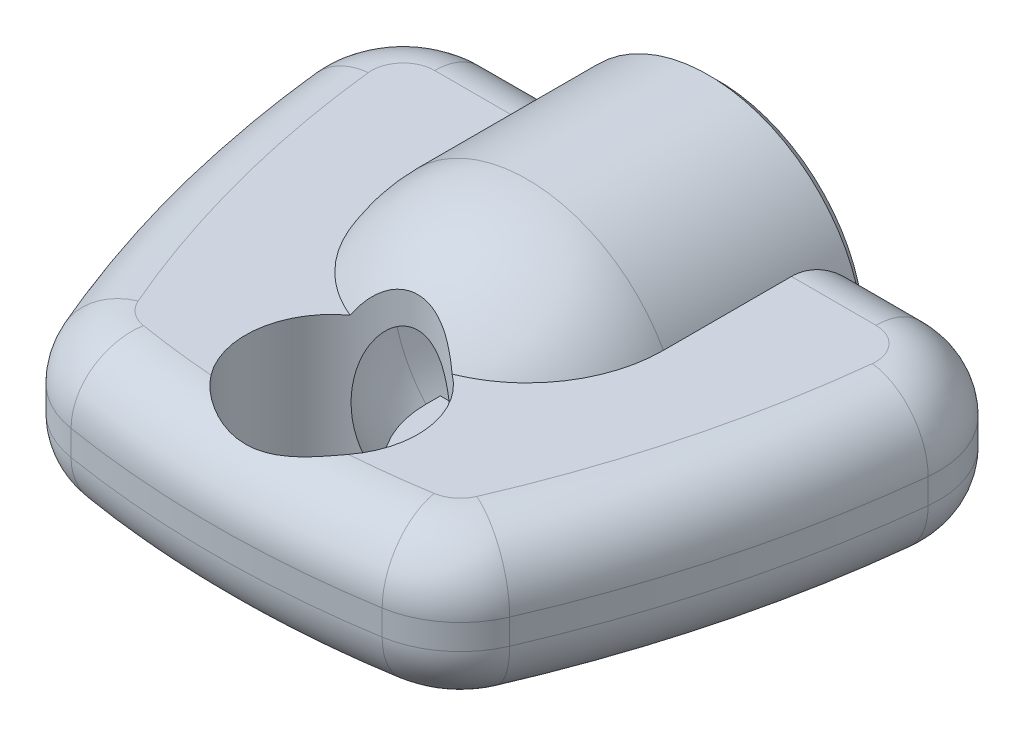
SolidWorks part; units mm, degrees
ref_plane "Front Plane" through (0, 0, 0) normal (0, 0, 1) x (1, 0, 0)
ref_plane "Top Plane" through (0, 0, 0) normal (0, 1, 0) x (1, 0, 0)
ref_plane "Right Plane" through (0, 0, 0) normal (1, 0, 0) x (0, 0, -1)
sketch "Sketch1" plane through (0, 0, 0) normal (0, 1, 0) x (1, 0, 0)
  line L0 (0, 0) -> (0, -80) construction
  line L1 (-35, 0) -> (35, 0)
  line L2 (0, -80) -> (35.1218, -80) construction
  line L3 (35.1218, -80) -> (44.768, -44) construction
  line L4 (24.6748, -78) -> (24.6748, -80) construction
  line L5 (36.033, -69.1354) -> (38.033, -69.1354) construction
  arc A0 (35, 0) -> (49.9097, -16.6432) centre (35, -15) cw
  arc A1 (-24.6748, -78) -> (24.6748, -78) centre (0, 73.2117) ccw
  arc A2 (24.6748, -78) -> (36.033, -69.1354) centre (22.2591, -63.1958) ccw
  arc A3 (36.033, -69.1354) -> (49.9097, -16.6432) centre (-132.2538, 3.4329) ccw
  arc A4 (-24.6748, -78) -> (-36.033, -69.1354) centre (-22.2591, -63.1958) cw
  arc A5 (-36.033, -69.1354) -> (-49.9097, -16.6432) centre (132.2538, 3.4329) cw
  arc A6 (-35, 0) -> (-49.9097, -16.6432) centre (-35, -15) ccw
  point P13 (37.9106, -67.9377)
  point P15 (40.8307, -80)
  point P18 (0, -40)
  point P25 (0, -76.0258)
  dimension "D4" = 15
  dimension "D6" = 15
  dimension "D1" = 2
  dimension "D2" = 80
  dimension "D3" = 35
  dimension "D5" = 4
  dimension "D7" = 105
extrude "Boss-Extrude1" add sketch "Sketch1" along normal blind 12 and the other way blind 12
fillet "Fillet1" radius 10 16 edges at (-31.4879, 12, 75.0207) (-44.9261, 12, 43.406) (-46.1725, 12, 4.9912) (0, 12, 0) (46.1725, 12, 4.9912) (44.9261, 12, 43.406) (31.4879, 12, 75.0207) (0, -12, 0) (-46.1725, -12, 4.9912) (-44.9261, -12, 43.406) (-31.4879, -12, 75.0207) (0, -12, 80) (31.4879, -12, 75.0207) (44.9261, -12, 43.406) (46.1725, -12, 4.9912) (0, 12, 80)
sketch "Sketch2" plane through (0, 0, 0) normal (0, 1, 0) x (1, 0, 0)
  line L0 (0, 0) -> (0, -55)
  line L1 (0, 0) -> (24.7, 0)
  line L2 (24.7, 0) -> (24.7, -30.3)
  line L3 (21.5, 0) -> (21.5, -30.3) construction
  arc A0 (24.7, -30.3) -> (0, -55) centre (0, -30.3) cw
  arc A1 (21.5, -30.3) -> (0, -51.8) centre (0, -30.3) cw construction
  dimension "D1" = 55
  dimension "D3" = 21.5
  dimension "D2" = 3.2
revolve "Revolve1" add sketch "Sketch2" angle 360 about L0
sketch "Sketch3" plane through (0, 0, 0) normal (0, 1, 0) x (1, 0, 0)
  line L0 (21.5, 0) -> (21.5, -30.3) construction
  line L1 (21.5, 0) -> (21.5, -30.3)
  line L2 (21.5, 0) -> (0, 0)
  line L3 (0, 0) -> (0, -51.8)
  arc A0 (0, -51.8) -> (21.5, -30.3) centre (0, -30.3) ccw construction
  arc A1 (0, -51.8) -> (21.5, -30.3) centre (0, -30.3) ccw
revolve "Cut-Revolve1" cut sketch "Sketch3" angle 360 about L3
ref_plane "Plane1" through (0, 0, 20) normal (0, 0, -1) x (-1, 0, 0)
sketch "Sketch4" plane through (0, 0, 20) normal (0, 0, -1) x (-1, 0, 0)
  line L0 (-16.0993, 14.25) -> (16.0993, 14.25)
  line L1 (-1000, 0) -> (49000, 0) construction
  line L2 (-16.0993, -14.25) -> (16.0993, -14.25)
  arc A0 (-16.0993, 14.25) -> (16.0993, 14.25) centre (0, 0) cw
  circle A1 centre (0, 0) radius 21.5 construction
  arc A2 (-16.0993, -14.25) -> (16.0993, -14.25) centre (0, 0) ccw
  dimension "D1" = 28.5
extrude "Boss-Extrude2" add sketch "Sketch4" against normal up to surface (10.3 mm away) up to face at (-21.5, 0, 30.3)
sketch "Sketch5" plane through (0, 0, 0) normal (0, 1, 0) x (1, 0, 0)
  line L0 (0, 0) -> (0, -80) construction
  line L1 (0, -80) -> (35.1218, -80) construction
  circle A0 centre (0, -61.3348) radius 13.6652
  arc A1 (0, -51.8) -> (21.5, -30.3) centre (0, -30.3) ccw construction
  point P5 (0, -75)
  point P7 (0, -47.6697)
  point P8 (0, 0)
  point P9 (8, -50.2562)
  dimension "D1" = 5
  dimension "D2" = 8
extrude "Cut-Extrude1" cut sketch "Sketch5" against normal through all both and the other way through all
chamfer "Chamfer1" distance 8 angle 45 2 edges at (0, 14.25, 20) (0, -14.25, 20)
chamfer "Chamfer2" distance 1.6 angle 45 2 edges at (0, -24.7, 0) (0, 24.7, 0)
